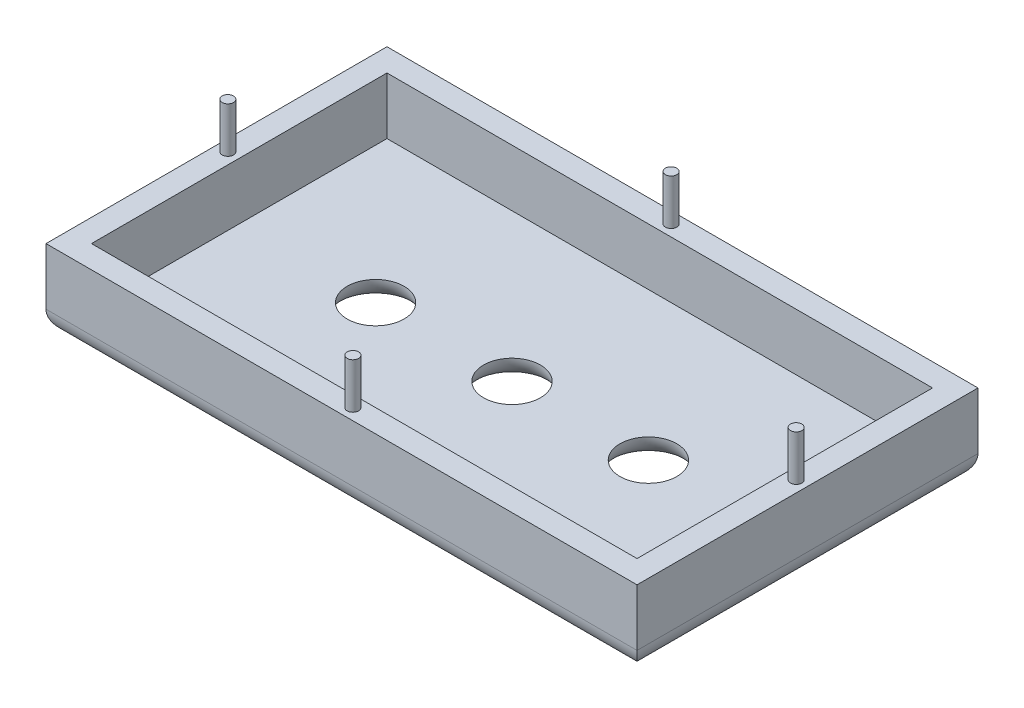
SolidWorks part; units mm, degrees
ref_plane "Front Plane" through (0, 0, 0) normal (0, 0, 1) x (1, 0, 0)
ref_plane "Top Plane" through (0, 0, 0) normal (0, 1, 0) x (1, 0, 0)
ref_plane "Right Plane" through (0, 0, 0) normal (1, 0, 0) x (0, 0, -1)
sketch "Sketch1" plane through (0, 0, 0) normal (0, 1, 0) x (1, 0, 0)
  line L1 (0, 0) -> (66.04, 0)
  line L2 (0, 0) -> (0, 38.1)
  line L3 (0, 38.1) -> (66.04, 38.1)
  line L4 (66.04, 0) -> (66.04, 38.1)
  dimension "D1" = 38.1
  dimension "D2" = 66.04
extrude "Boss-Extrude3" add sketch "Sketch1" along normal blind 17.78
sketch "Sketch3" plane through (0, 17.78, 0) normal (0, 1, 0) x (1, 0, 0)
  line L0 (0, 38.1) -> (0, 0) construction
  line L1 (2.54, 35.56) -> (63.5, 35.56)
  line L2 (2.54, 35.56) -> (2.54, 2.54)
  line L3 (2.54, 2.54) -> (63.5, 2.54)
  line L4 (63.5, 35.56) -> (63.5, 2.54)
  line L5 (66.04, 0) -> (66.04, 38.1) construction
  line L6 (66.04, 38.1) -> (0, 38.1) construction
  line L7 (0, 0) -> (66.04, 0) construction
  dimension "D1" = 2.54
  dimension "D2" = 2.54
  dimension "D3" = 2.54
  dimension "D4" = 2.54
extrude "Cut-Extrude1" cut sketch "Sketch3" against normal blind 15.24
sketch "Sketch4" plane through (66.04, 0, 0) normal (1, 0, 0) x (0, 0, -1)
  line L0 (38.1, 17.78) -> (38.1, 0) construction
  line L1 (0, 17.78) -> (38.1, 17.78)
  line L2 (0, 17.78) -> (0, 8.89)
  line L3 (0, 8.89) -> (38.1, 8.89)
  line L4 (38.1, 17.78) -> (38.1, 8.89)
  line M6 (38.1, 0) -> (38.1, 17.78)
  line M7 (38.1, 17.78) -> (0, 17.78)
  line M8 (0, 17.78) -> (0, 0)
extrude "Cut-Extrude2" cut sketch "Sketch4" against normal blind 66.04 contours L3 M8 M6 M7 | L2 L1 L4 L3 region at (66.04, 13.335, -19.05)
sketch "Sketch5" plane through (0, 8.89, 0) normal (0, 1, 0) x (1, 0, 0)
  line L0 (0, 0) -> (0, 38.1) construction
  line L1 (63.5, 35.56) -> (2.54, 35.56) construction
  line L2 (2.54, 2.54) -> (63.5, 2.54) construction
  line L3 (2.54, 35.56) -> (2.54, 2.54) construction
  line L4 (0, 38.1) -> (66.04, 38.1) construction
  line L5 (63.5, 2.54) -> (63.5, 35.56) construction
  line L6 (0, 0) -> (66.04, 0) construction
  circle A0 centre (33.02, 36.83) radius 0.635
  circle A1 centre (33.02, 1.27) radius 0.635
  circle A2 centre (1.27, 19.05) radius 0.635
  circle A3 centre (64.77, 19.05) radius 0.635
  dimension "D3" = 1.27
  dimension "D4" = 1.27
  dimension "D7" = 1.27
  dimension "D10" = 1.27
  dimension "D1" = 33.02
  dimension "D2" = 1.27
  dimension "D5" = 1.27
  dimension "D6" = 33.02
  dimension "D8" = 1.27
  dimension "D9" = 19.05
  dimension "D11" = 1.27
  dimension "D12" = 19.05
extrude "Boss-Extrude4" add sketch "Sketch5" along normal blind 5.08
sketch "Sketch6" plane through (0, 0, 0) normal (0, -1, 0) x (1, 0, 0)
  line L0 (0, -38.1) -> (0, 0) construction
  line L1 (66.04, -38.1) -> (0, -38.1) construction
  circle A0 centre (17.78, -19.05) radius 3.175
  circle A1 centre (33.02, -19.05) radius 3.175
  circle A2 centre (48.26, -19.05) radius 3.175
  dimension "D3" = 6.35
  dimension "D6" = 6.35
  dimension "D8" = 6.35
  dimension "D1" = 33.02
  dimension "D2" = 19.05
  dimension "D4" = 17.78
  dimension "D5" = 19.05
  dimension "D7" = 48.26
  dimension "D9" = 19.05
extrude "Cut-Extrude4" cut sketch "Sketch6" against normal blind 2.54
fillet "Fillet1" radius 2.54 7 edges at (33.02, 0, 0) (66.04, 0, -19.05) (33.02, 0, -38.1) (0, 0, -19.05) (48.26, 0, -22.225) (33.02, 0, -22.225) (17.78, 0, -22.225)
